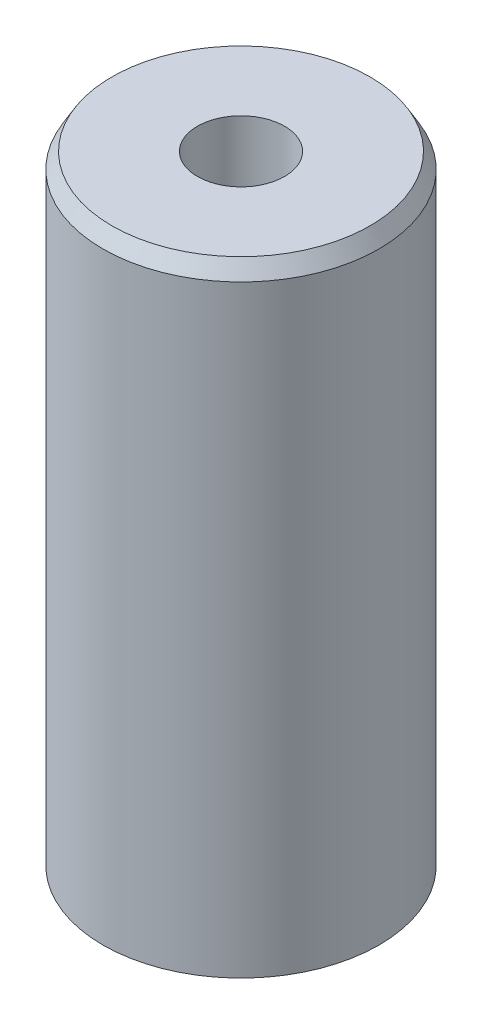
SolidWorks part; units mm, degrees
ref_plane "Front Plane" through (0, 0, 0) normal (0, 0, 1) x (1, 0, 0)
ref_plane "Top Plane" through (0, 0, 0) normal (0, 1, 0) x (1, 0, 0)
ref_plane "Right Plane" through (0, 0, 0) normal (1, 0, 0) x (0, 0, -1)
sketch "Sketch1" plane through (0, 0, 0) normal (0, 1, 0) x (1, 0, 0)
  circle A0 centre (0, 0) radius 12.5
  dimension "SHAFT_OD" = 25
extrude "Boss-Extrude1" add sketch "Sketch1" along normal blind 56.8151
sketch "Sketch2" plane through (0, 0, 0) normal (0, 1, 0) x (1, 0, 0)
  circle A0 centre (0, 0) radius 3.9463
  dimension "BORE_D" = 7.8926
extrude "Cut-Extrude1" cut sketch "Sketch2" along normal through all
chamfer "Chamfer1" distance 1.408 angle 30 2 edges at (0, 56.8151, 12.5) (0, 0, 12.5) first distance on face at (0, 56.8151, 12.5) first distance on face at (0, 0, 3.9463)
